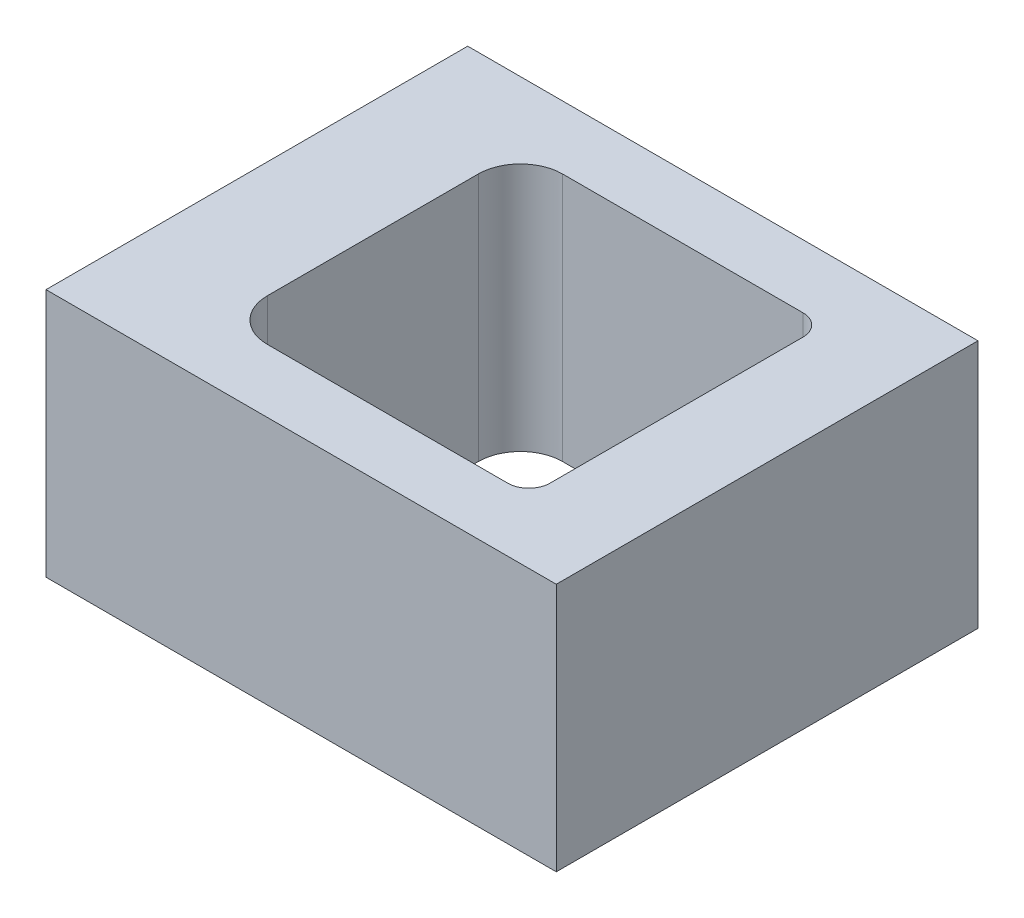
SolidWorks part; units mm, degrees
ref_plane "Front Plane" through (0, 0, 0) normal (0, 0, 1) x (1, 0, 0)
ref_plane "Top Plane" through (0, 0, 0) normal (0, 1, 0) x (1, 0, 0)
ref_plane "Right Plane" through (0, 0, 0) normal (1, 0, 0) x (0, 0, -1)
sketch "Sketch1" plane through (0, 0, 0) normal (0, 1, 0) x (1, 0, 0)
  line L1 (-76.835, -63.5) -> (76.835, -63.5)
  line L2 (-76.835, -63.5) -> (-76.835, 63.5)
  line L3 (-76.835, 63.5) -> (76.835, 63.5)
  line L4 (76.835, -63.5) -> (76.835, 63.5)
  line L5 (-76.835, -63.5) -> (76.835, 63.5) construction
  line L6 (-76.835, 63.5) -> (76.835, -63.5) construction
  line L14 (-41.91, 31.75) -> (-41.91, -31.75) construction
  line L15 (43.18, -44.45) -> (-29.21, -44.45) construction
  line L16 (49.53, 38.1) -> (49.53, -38.1) construction
  line L17 (43.18, 44.45) -> (-29.21, 44.45) construction
  line L18 (-41.91, 31.75) -> (-41.91, -31.75)
  line L19 (43.18, -44.45) -> (-29.21, -44.45)
  line L20 (49.53, 38.1) -> (49.53, -38.1)
  line L21 (43.18, 44.45) -> (-29.21, 44.45)
  arc A8 (-41.91, -31.75) -> (-29.21, -44.45) centre (-29.21, -31.75) ccw construction
  arc A9 (43.18, -44.45) -> (49.53, -38.1) centre (43.18, -38.1) ccw construction
  arc A10 (49.53, 38.1) -> (43.18, 44.45) centre (43.18, 38.1) ccw construction
  arc A11 (-29.21, 44.45) -> (-41.91, 31.75) centre (-29.21, 31.75) ccw construction
  arc A12 (-41.91, -31.75) -> (-29.21, -44.45) centre (-29.21, -31.75) ccw
  arc A13 (43.18, -44.45) -> (49.53, -38.1) centre (43.18, -38.1) ccw
  arc A14 (49.53, 38.1) -> (43.18, 44.45) centre (43.18, 38.1) ccw
  arc A15 (-29.21, 44.45) -> (-41.91, 31.75) centre (-29.21, 31.75) ccw
  point P0 (0, 0)
  dimension "D1" = 127
  dimension "D2" = 153.67
extrude "Boss-Extrude1" add sketch "Sketch1" along normal blind 75.0062
